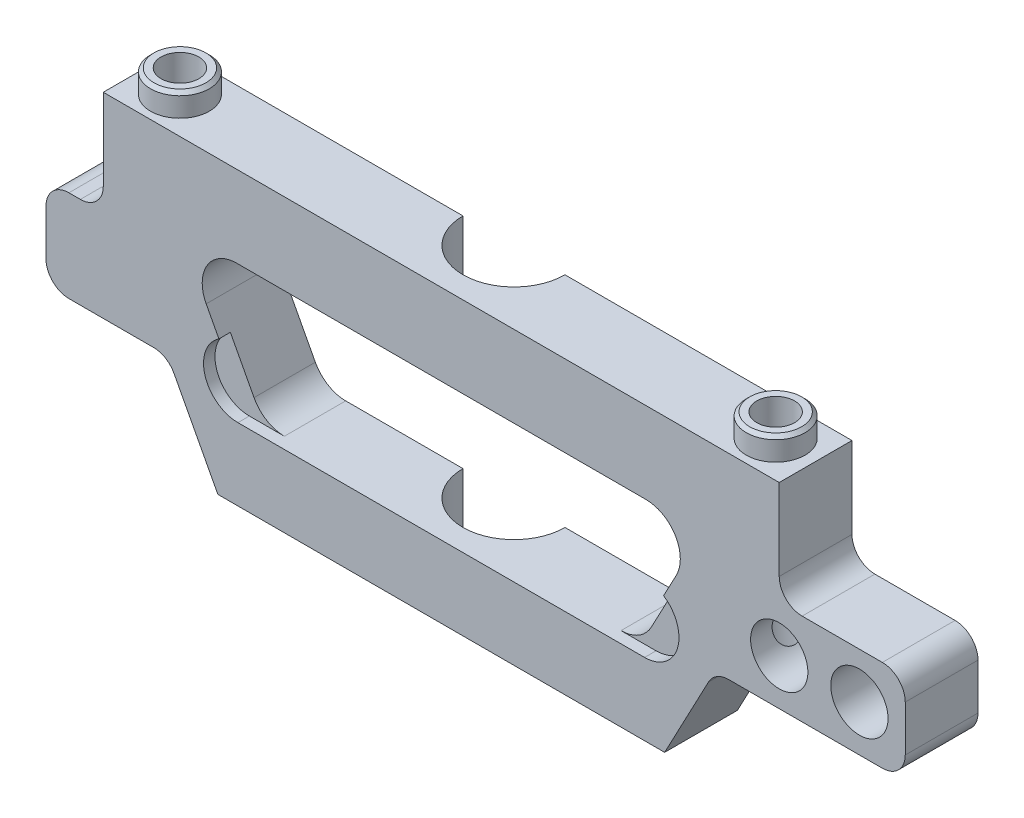
SolidWorks part; units mm, degrees
ref_plane "Front Plane" through (0, 0, 0) normal (0, 0, 1) x (1, 0, 0)
ref_plane "Top Plane" through (0, 0, 0) normal (0, 1, 0) x (1, 0, 0)
ref_plane "Right Plane" through (0, 0, 0) normal (1, 0, 0) x (0, 0, -1)
sketch "Sketch1" plane through (0, 0, 0) normal (0, 0, 1) x (1, 0, 0)
  line L0 (0, 0) -> (0, 26480.0211) construction
  line L1 (-29.5, 0) -> (29.5, 0)
  line L2 (29.5, 0) -> (29.5, -6.5)
  line L3 (29.5, -6.5) -> (19.5, -25.4)
  line L4 (19.5, -25.4) -> (-19.5, -25.4)
  line L5 (-19.5, -25.4) -> (-29.5, -6.5)
  line L6 (-29.5, -6.5) -> (-29.5, 0)
  point P5 (0, 0)
  point P10 (0, -25.4)
  dimension "D1" = 59
  dimension "D2" = 25.4
  dimension "D3" = 6.5
  dimension "D4" = 39
extrude "Boss-Extrude1" add sketch "Sketch1" against normal blind 6.35
sketch "Sketch2" plane through (0, 0, 0) normal (0, 0, 1) x (1, 0, 0)
  line L9 (-24.5502, -3.881) -> (-14.5502, -22.781)
  line L10 (-24.5502, -3.881) -> (-14.5502, -22.781) construction
  line L12 (-19.5, -19.1) -> (19.5, -19.1)
  line L13 (-19.5, -19.1) -> (19.5, -19.1) construction
  line L15 (14.5502, -22.781) -> (24.5502, -3.881)
  line L16 (14.5502, -22.781) -> (24.5502, -3.881) construction
  line L17 (-22.847, -7.1) -> (-16.4978, -19.1)
  line L18 (29.5, -7.1) -> (-29.5, -7.1)
  line L19 (29.5, -7.1) -> (-29.5, -7.1) construction
  line L20 (-16.4978, -19.1) -> (16.4978, -19.1)
  line L21 (16.4978, -19.1) -> (22.847, -7.1)
  line L22 (22.847, -7.1) -> (-22.847, -7.1)
  dimension "D1" = 5.6
  dimension "D2" = 6.3
  dimension "D3" = 5.6
  dimension "D4" = 7.1
extrude "Cut-Extrude1" cut sketch "Sketch2" against normal through all both and the other way through all
sketch "Sketch3" plane through (0, 0, 0) normal (0, 1, 0) x (1, 0, 0)
  line L0 (29.5, 6.35) -> (-29.5, 6.35) construction
  circle A0 centre (0, 6.35) radius 4.45
  dimension "D1" = 8.9
extrude "Cut-Extrude2" cut sketch "Sketch3" against normal through all
fillet "Fillet1" radius 3 4 edges at (22.847, -7.1, -3.175) (16.4978, -19.1, -3.175) (-22.847, -7.1, -3.175) (-16.4978, -19.1, -3.175)
sketch "Sketch4" plane through (0, 0, 0) normal (0, 1, 0) x (1, 0, 0)
  line L1 (0, 0) -> (0, 50000) construction
  line L2 (29.5, 6.35) -> (4.45, 6.35) construction
  circle A0 centre (-26, 3.19) radius 1.65
  circle A1 centre (-26, 3.19) radius 2.565
  circle A2 centre (26, 3.19) radius 1.65
  circle A3 centre (26, 3.19) radius 2.565
  dimension "D1" = 3.3
  dimension "D2" = 5.13
  dimension "D3" = 3.16
  dimension "D4" = 52
extrude "Boss-Extrude2" add sketch "Sketch4" along normal blind 2
sketch "Sketch6" plane through (0, 0, 0) normal (0, 0, 1) x (1, 0, 0)
  line L0 (0, 0) -> (0, 50000) construction
  line L1 (17.75, -16.1) -> (-17.75, -16.1) construction
  line L2 (17.75, -19.1) -> (-17.75, -19.1)
  line L3 (17.75, -13.1) -> (-17.75, -13.1)
  line L4 (-14.691, -19.1) -> (14.691, -19.1) construction
  arc A0 (17.75, -19.1) -> (17.75, -13.1) centre (17.75, -16.1) ccw
  arc A1 (-17.75, -13.1) -> (-17.75, -19.1) centre (-17.75, -16.1) ccw
  point P5 (0, -16.1)
  dimension "D1" = 3
  dimension "D2" = 35.5
extrude "Cut-Extrude4" cut sketch "Sketch6" against normal blind 1
ref_plane "Plane1" through (0, -13.1, 0) normal (0, 1, 0) x (1, 0, 0)
sketch "Sketch7" plane through (0, 0, -6.35) normal (0, 0, -1) x (-1, 0, 0)
  line L0 (-29.5, 0) -> (-4.45, 0) construction
  line L1 (-12, -3.55) -> (12, -3.55) construction
  line L2 (-12, -3.55) -> (-12, -22.25) construction
  line L3 (-12, -22.25) -> (12, -22.25) construction
  line L4 (12, -3.55) -> (12, -22.25) construction
  line L5 (-4.45, -25.4) -> (-19.5, -25.4) construction
  circle A0 centre (-12, -3.55) radius 1.5
  circle A1 centre (-12, -22.25) radius 1.5
  circle A2 centre (12, -22.25) radius 1.5
  circle A3 centre (12, -3.55) radius 1.5
  point P4 (0, -3.55)
  dimension "D4" = 3
  dimension "D1" = 3.55
  dimension "D2" = 3.15
  dimension "D3" = 24
extrude "Cut-Extrude5" cut sketch "Sketch7" against normal blind 3
chamfer "Chamfer1" distance 0.3 angle 45 4 edges at (10.5, -22.25, -6.35) (-13.5, -22.25, -6.35) (-13.5, -3.55, -6.35) (10.5, -3.55, -6.35)
chamfer "Chamfer2" distance 0.3 angle 45 2 edges at (-26, 2, -0.625) (26, 2, -0.625)
sketch "Sketch8" plane through (0, 0, -6.35) normal (0, 0, -1) x (-1, 0, 0)
  line L0 (-29.5, -6.5) -> (-29.5, -9.1)
  line L1 (-29.5, -9.1) -> (-40.5, -9.1)
  line L2 (-40.5, -9.1) -> (-40.5, -17.1)
  line L3 (-40.5, -17.1) -> (-23.8915, -17.1)
  line L4 (-19.5, -25.4) -> (-29.5, -6.5) construction
  line L5 (-23.8915, -17.1) -> (-29.5, -6.5)
  line L6 (29.5, -6.5) -> (23.8915, -17.1)
  line L7 (29.5, -6.5) -> (19.5, -25.4) construction
  line L8 (23.8915, -17.1) -> (34.5, -17.1)
  line L9 (34.5, -17.1) -> (34.5, -9.1)
  line L10 (34.5, -9.1) -> (29.5, -9.1)
  line L11 (29.5, -9.1) -> (29.5, -6.5)
  line L12 (3.4925, -13.1) -> (-3.4925, -13.1) construction
  circle A0 centre (-36.5, -13.1) radius 2.5
  circle A1 centre (-29.5, -13.1) radius 2.5
  point P13 (34.5, -13.1)
  point P19 (-40.5, -13.1)
  point P24 (0, 0)
  point P25 (0, 0)
  point P26 (0, 0)
  dimension "D5" = 5
  dimension "D1" = 8
  dimension "D2" = 11
  dimension "D3" = 5
  dimension "D4" = 7
  dimension "D6" = 4
extrude "Boss-Extrude3" add sketch "Sketch8" against normal up to surface (6.35 mm away) up to face at (0, -12.7924, 0)
sketch "Sketch5" plane through (0, 0, 0) normal (0, 1, 0) x (1, 0, 0)
  circle A0 centre (26, 3.19) radius 1.65 construction
  circle A1 centre (-26, 3.19) radius 1.65 construction
  circle A2 centre (26, 3.19) radius 1.65
  circle A3 centre (-26, 3.19) radius 1.65
extrude "Cut-Extrude3" cut sketch "Sketch5" against normal through all
fillet "Fillet2" radius 2 4 edges at (-34.5, -17.1, -3.175) (-34.5, -9.1, -3.175) (40.5, -17.1, -3.175) (40.5, -9.1, -3.175)
fillet "Fillet3" radius 2 4 edges at (-23.8915, -17.1, -3.175) (-29.5, -9.1, -3.175) (23.8915, -17.1, -3.175) (29.5, -9.1, -3.175)
